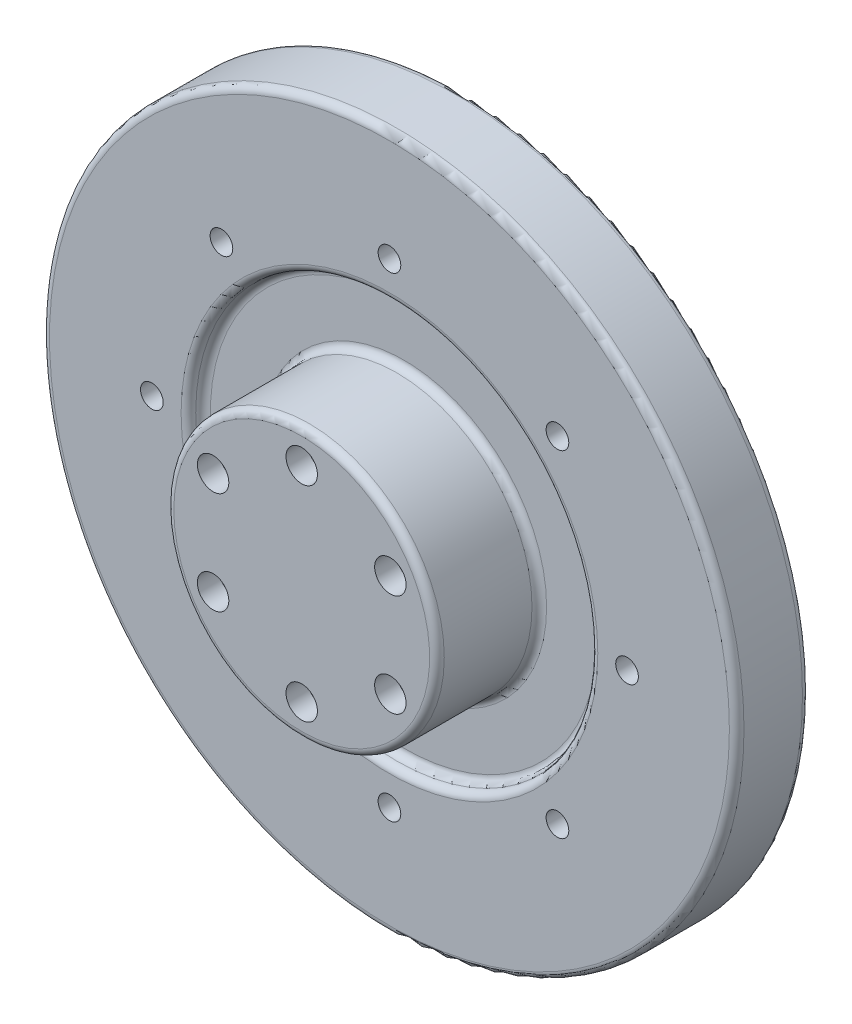
SolidWorks part; units mm, degrees
material "Custom PLA"
ref_plane "Front Plane" through (0, 0, 0) normal (0, 0, 1) x (1, 0, 0)
ref_plane "Top Plane" through (0, 0, 0) normal (0, 1, 0) x (1, 0, 0)
ref_plane "Right Plane" through (0, 0, 0) normal (1, 0, 0) x (0, 0, -1)
sketch "Sketch1" plane through (0, 0, 0) normal (0, 0, 1) x (1, 0, 0)
  circle A0 centre (0, 0) radius 47.5
  circle A1 centre (0, 0) radius 41.5 construction
  circle A2 centre (0, 41.5) radius 2.25
  dimension "D1" = 95
  dimension "D2" = 83
  dimension "D3" = 4.5
extrude "Boss-Extrude1" add sketch "Sketch1" along normal blind 10 contours A0
sketch "Sketch5" plane through (0, 0, 0) normal (0, 1, 0) x (1, 0, 0)
  line L0 (0, 0) -> (0, -22)
  line L1 (0, -22) -> (18.5, -22)
  line L2 (18.5, -22) -> (18.5, 0)
  line L3 (47.5, 0) -> (-47.5, 0) construction
  line L4 (18.5, 0) -> (0, 0)
  line L5 (-47.5, -10) -> (47.5, -10) construction
  dimension "D1" = 18.5
  dimension "D2" = 12
revolve "Revolve1" add sketch "Sketch5" angle 360 about L0
fillet "Fillet2" [suppressed] radius 10
sketch "Sketch6" plane through (0, 0, 0) normal (0, 0, -1) x (-1, 0, 0)
  circle A0 centre (0, 0) radius 17.5
  dimension "D1" = 35
extrude "Cut-Extrude7" cut sketch "Sketch6" against normal blind 19
sketch "Sketch7" plane through (0, 0, 19) normal (0, 0, -1) x (-1, 0, 0)
  circle A0 centre (0, 0) radius 14 construction
  circle A1 centre (0, 14) radius 2.15
  dimension "D1" = 28
  dimension "D2" = 4.3
extrude "Cut-Extrude8" cut sketch "Sketch7" against normal blind 10
pattern_circular "CirPattern2" count 6 over 360 about axis through (0, 0, 19) along (0, 0, -1) of "Cut-Extrude8", "Cut-Extrude7"
sketch "Sketch8" plane through (0, 0, 10) normal (0, 0, -1) x (-1, 0, 0)
  circle A0 centre (0, 0) radius 32.5 construction
  circle A1 centre (0, 32.5) radius 1.55
  dimension "D1" = 65
  dimension "D2" = 3.1
extrude "Cut-Extrude9" cut sketch "Sketch8" along normal blind 4.7
pattern_circular "CirPattern3" count 8 over 360 about axis through (0, 0, 0) along (0, 0, 1) of "Cut-Extrude9"
sketch "Sketch10" plane through (0, 0, 10) normal (0, 0, 1) x (1, 0, 0)
  circle A0 centre (0, 0) radius 18.5
  circle A1 centre (0, 0) radius 27.5
  dimension "D1" = 55
  dimension "D2" = 37
extrude "Cut-Extrude10" cut sketch "Sketch10" against normal blind 2
sketch "Sketch12" plane through (0, 0, 0) normal (0, 0, -1) x (-1, 0, 0)
  line L0 (0, 33.3593) -> (0, -40.9676) construction
  circle A0 centre (0, 26.5) radius 2.975
  circle A2 centre (0, 0) radius 26.5 construction
  dimension "D1" = 5.95
  dimension "D2" = 53
extrude "Cut-Extrude11" cut sketch "Sketch12" against normal blind 4.7
pattern_circular "CirPattern4" count 6 over 360 about axis through (0, 0, 0) along (0, 0, 1) of "Cut-Extrude11"
sketch "Sketch13" plane through (0, 0, 19) normal (0, 0, -1) x (-1, 0, 0)
  circle A0 centre (0, 0) radius 17.5 construction
  circle A2 centre (-12.1244, 7) radius 2.15 construction
  point P0 (-15.2968, 8.5005)
  point P1 (-14.0946, 7.8605)
fillet "Fillet3" radius 1 7 edges at (27.5, 0, 10) (27.5, 0, 8) (-17.5, 0, 0) (47.5, 0, 0) (47.5, 0, 10) (18.5, 0, 8) (-18.5, 0, 22)
fillet "Fillet4" radius 0.5 1 edges at (-17.5, 0, 19)
